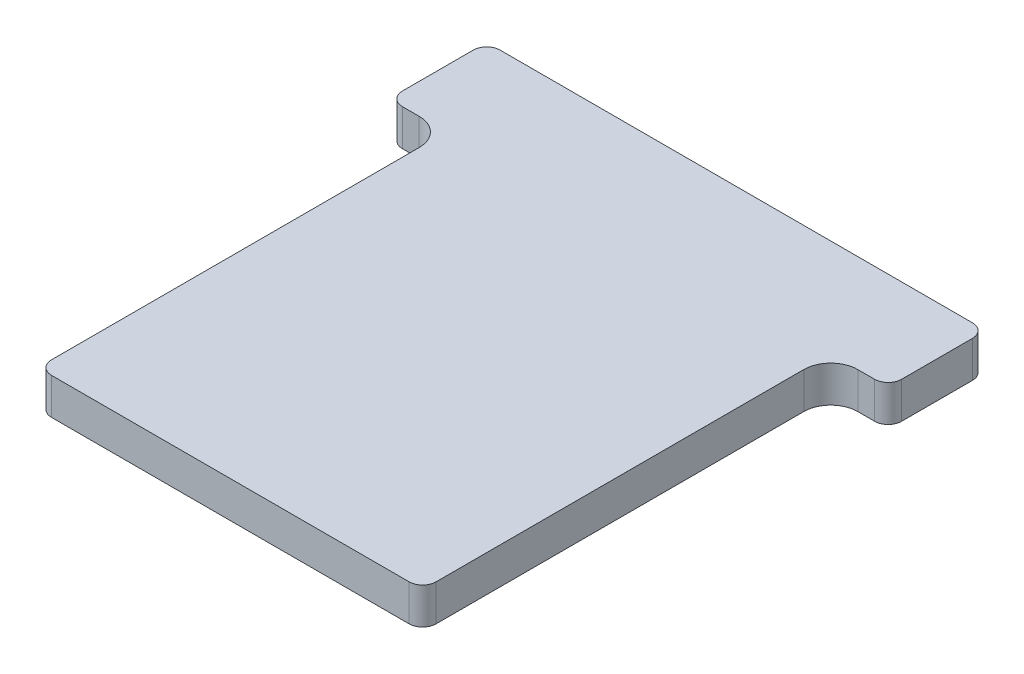
SolidWorks part; units mm, degrees
ref_plane "Front Plane" through (0, 0, 0) normal (0, 0, 1) x (1, 0, 0)
ref_plane "Top Plane" through (0, 0, 0) normal (0, 1, 0) x (1, 0, 0)
ref_plane "Right Plane" through (0, 0, 0) normal (1, 0, 0) x (0, 0, -1)
sketch "Sketch1" plane through (0, 0, 0) normal (0, 1, 0) x (1, 0, 0)
  line L0 (-14.25, 15.125) -> (-18.5, 15.125)
  line L1 (-14.25, -15.125) -> (14.25, -15.125)
  line L2 (-14.25, -15.125) -> (-14.25, 15.125)
  line L3 (-18.5, 22.375) -> (-18.5, 15.125)
  line L4 (14.25, -15.125) -> (14.25, 15.125)
  line L5 (-14.25, -15.125) -> (14.25, 15.125) construction
  line L6 (-14.25, 15.125) -> (14.25, -15.125) construction
  line L7 (14.25, 15.125) -> (18.5, 15.125)
  line L8 (-18.5, 22.375) -> (18.5, 22.375)
  line L9 (18.5, 22.375) -> (18.5, 15.125)
  circle A0 centre (-1.25, 18.375) radius 1.5 construction
  point P0 (0, 0)
  dimension "D7" = 3
  dimension "D1" = 28.5
  dimension "D2" = 7.25
  dimension "D3" = 37.5
  dimension "D4" = 37
  dimension "D5" = 13
  dimension "D8" = 4
extrude "Boss-Extrude1" add sketch "Sketch1" along normal blind 2.7
ref_plane "plunger plane" through (0, 1.35, 0) normal (0, 1, 0) x (-1, 0, 0)
ref_plane "centre plane" through (0, 0, 0) normal (1, 0, 0) x (0, 0, -1)
ref_axis "Axis1" through (0, 1.35, -21.8545) along (0, 0, 1)
sketch "Sketch15" plane through (0, 2.7, 0) normal (0, 1, 0) x (1, 0, 0)
  line L0 (-14.25, 2.19) -> (-14.25, 15.375)
  line L1 (-14.25, 15.125) -> (-14.25, -15.125) construction
  line L2 (18.5, 22.375) -> (-18.5, 22.375) construction
  arc A0 (-14.25, 15.375) -> (-14.25, 2.19) centre (-6.7308, 8.7825) ccw
  dimension "D1" = 10
  dimension "D2" = 7
extrude "Cut-Extrude2" [suppressed] cut sketch "Sketch15" against normal through all
mirror "Mirror1" [suppressed] about plane through (0, 0, 0) normal (1, 0, 0)
fillet "Fillet5" [suppressed] radius 1
ref_axis "Axis2" through (-33, 1.35, -15.125) along (1, 0, 0)
ref_plane "Plane1" through (0, 0, -3.625) normal (0, 0, -1) x (-1, 0, 0)
fillet "Fillet6" radius 1 6 edges at (14.25, 1.35, 15.125) (-14.25, 1.35, 15.125) (18.5, 1.35, -22.375) (18.5, 1.35, -15.125) (-18.5, 1.35, -15.125) (-18.5, 1.35, -22.375)
fillet "Fillet7" radius 2 2 edges at (14.25, 1.35, -15.125) (-14.25, 1.35, -15.125)
